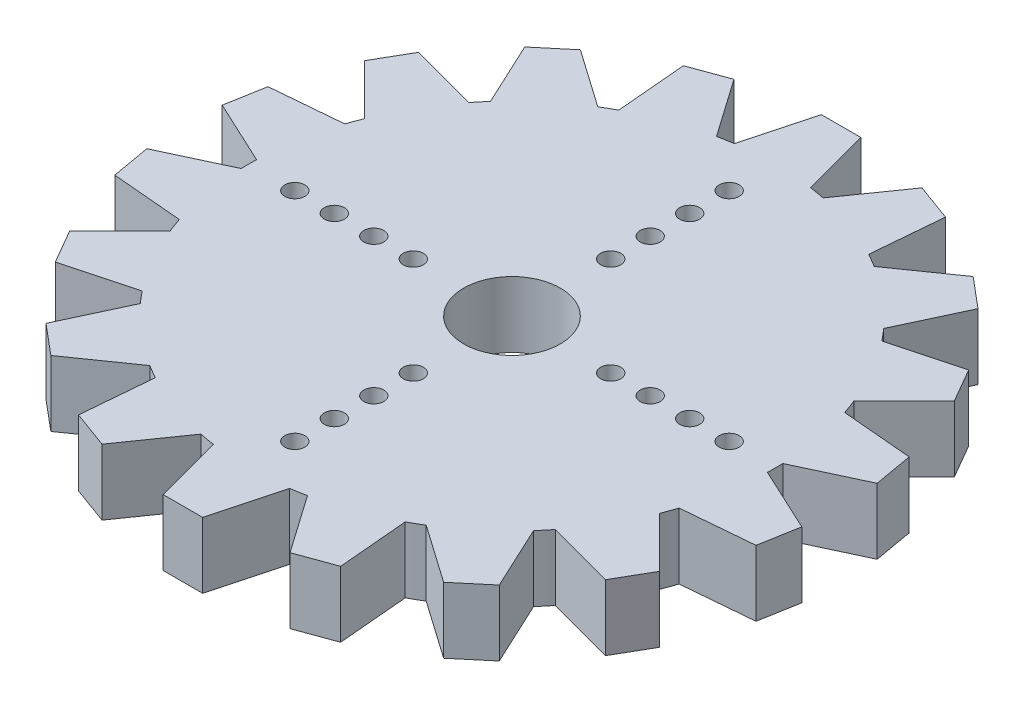
SolidWorks part; units mm, degrees
ref_plane "Front Plane" through (0, 0, 0) normal (0, 0, 1) x (1, 0, 0)
ref_plane "Top Plane" through (0, 0, 0) normal (0, 1, 0) x (1, 0, 0)
ref_plane "Right Plane" through (0, 0, 0) normal (1, 0, 0) x (0, 0, -1)
sketch "Sketch2" plane through (0, 0, 0) normal (0, 1, 0) x (1, 0, 0)
  line L0 (-3.1077, 19) -> (3.0419, 19)
  line L1 (3.1077, 19) -> (1.5, 25)
  line L2 (1.5, 25) -> (-1.5, 25)
  line L3 (-1.5, 25) -> (-3.1077, 19)
  circle A0 centre (0, 0) radius 20
  dimension "D1" = 25
  dimension "D2" = 6
  dimension "D3" = 75
  dimension "D4" = 75
  dimension "D5" = 3
  dimension "D6" = 1.5
extrude "Boss-Extrude1" add sketch "Sketch2" along normal blind 5
extrude "Boss-Extrude2" add sketch "Sketch2<3>" along normal blind 5 contours A0 L1 L2 L3 region at (0, 0, -22.2016)
sketch "Sketch2<3>" plane through (0, 0, 0) normal (0, 1, 0) x (1, 0, 0) same geometry as "Sketch2"
pattern_circular "CirPattern1" count 18 over 360 about axis through (0, 5, 0) along (0, -1, 0) of "Boss-Extrude2" reverse direction yes
sketch "Sketch3" plane through (0, 0, 0) normal (0, 1, 0) x (1, 0, 0)
  circle A0 centre (0, 0) radius 3.675
  circle A1 centre (7.5, 0) radius 0.762
  circle A2 centre (10.5, 0) radius 0.762
  circle A3 centre (13.5, 0) radius 0.762
  circle A4 centre (16.5, 0) radius 0.762
  dimension "D1" = 7.5
  dimension "D2" = 3
  dimension "D3" = 3
  dimension "D5" = 7.35
  dimension "D4" = 3
extrude "Cut-Extrude1" cut sketch "Sketch3" along normal through all
pattern_circular "CirPattern2" count 4 over 360 about axis through (0, 5, 0) along (0, -1, 0) of "Cut-Extrude1"
